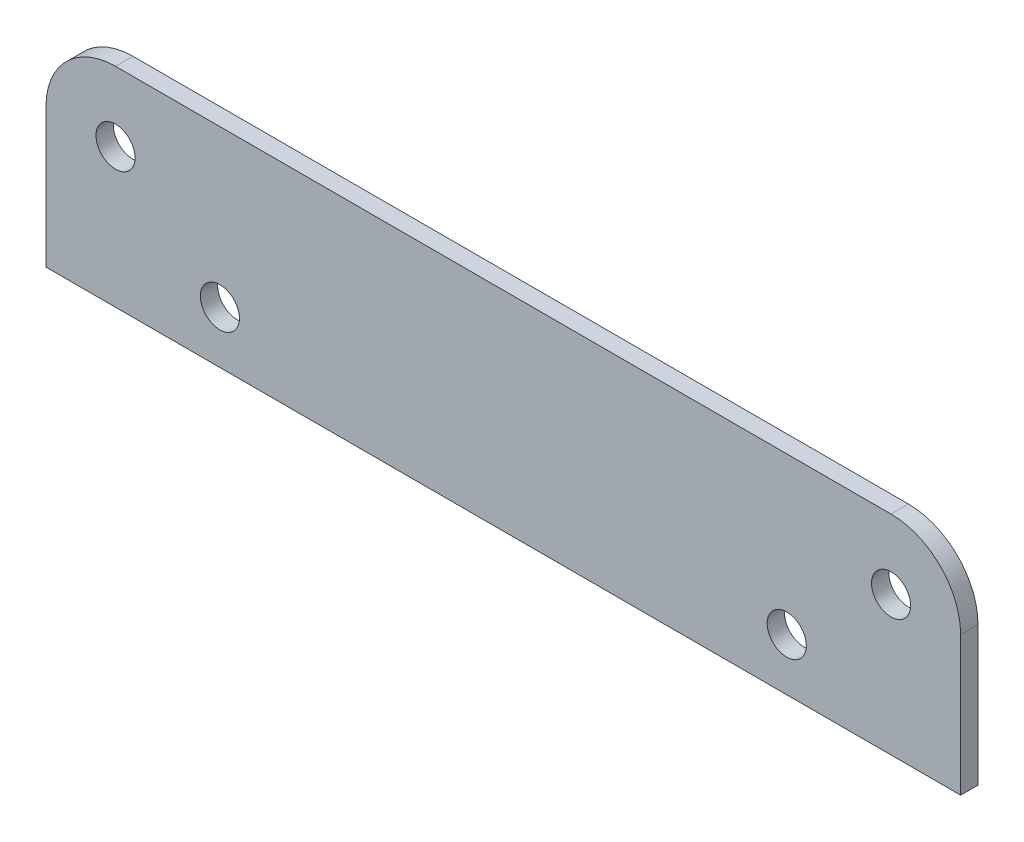
SolidWorks part; units mm, degrees
material "ABS PC"
ref_plane "Front Plane" through (0, 0, 0) normal (0, 0, 1) x (1, 0, 0)
ref_plane "Top Plane" through (0, 0, 0) normal (0, 1, 0) x (1, 0, 0)
ref_plane "Right Plane" through (0, 0, 0) normal (1, 0, 0) x (0, 0, -1)
sketch "Sketch1" plane through (0, 0, 0) normal (0, 0, 1) x (1, 0, 0)
  line L2 (83.5025, -1713.1435) -> (-83.5025, -1713.1435)
  line L3 (83.5025, -1713.1435) -> (83.5025, -1675.0435)
  line L4 (83.5025, -1675.0435) -> (-83.5025, -1675.0435)
  line L5 (-83.5025, -1713.1435) -> (-83.5025, -1675.0435)
  line L6 (-83.5025, -1862.3685) -> (-83.5025, -1713.1435) construction
  dimension "D1" = 38.1
extrude "Boss-Extrude1" add sketch "Sketch1" along normal blind 3.175
fillet "Fillet1" radius 12.7 2 edges at (83.5025, -1675.0435, 1.5875) (-83.5025, -1675.0435, 1.5875)
hole_wizard "1/4 Clearance Hole1" positions "Sketch2" profile "Sketch3" hole size "1/4" standard "ANSI Inch" end condition up to next
sketch "Sketch2" plane through (0, 0, 3.175) normal (0, 0, 1) x (1, 0, 0)
  line L2 (0, -1675.0435) -> (0, -1713.1435) construction
  line L3 (70.8025, -1675.0435) -> (-70.8025, -1675.0435) construction
  line L4 (-7.747, -1713.1435) -> (7.747, -1713.1435) construction
  line L5 (-83.5025, -1713.1435) -> (83.5025, -1713.1435) construction
  line L6 (83.5025, -1713.1435) -> (83.5025, -1687.7435) construction
  point P0 (-70.8025, -1687.7435)
  point P3 (70.8025, -1687.7435)
  point P25 (51.7525, -1703.6185)
  point P33 (-51.7525, -1703.6185)
  dimension "D1" = 9.525
  dimension "D2" = 31.75
sketch "Sketch3" plane through (-70.8025, -1687.7435, 3.175) normal (1, 0, 0) x (0, -1, 0)
  line L0 (0, 0) -> (0, 3.175)
  line L1 (0, 3.175) -> (3.5712, 3.175)
  line L2 (3.5712, 3.175) -> (3.5712, 0)
  line L5 (3.5712, 0) -> (0, 0)
  line L11 (0, -6.35) -> (0, 107.95) construction
  dimension "Thru Hole Dia." = 7.1425
  dimension "Thru Hole Depth" = 3.175
